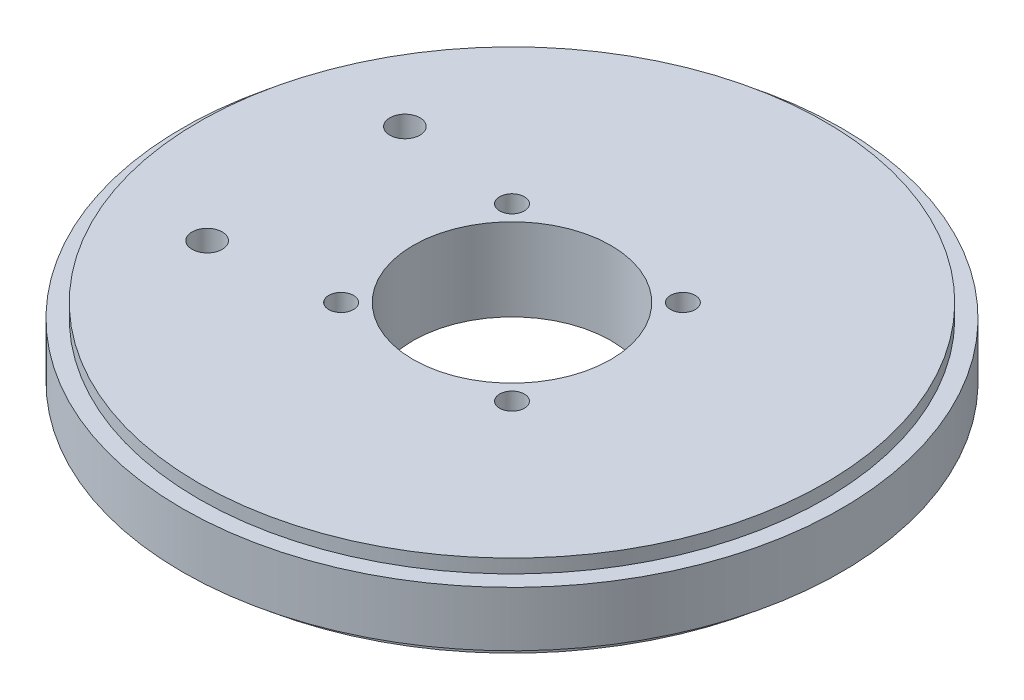
SolidWorks part; units mm, degrees
ref_plane "Front Plane" through (0, 0, 0) normal (0, 0, 1) x (1, 0, 0)
ref_plane "Top Plane" through (0, 0, 0) normal (0, 1, 0) x (1, 0, 0)
ref_plane "Right Plane" through (0, 0, 0) normal (1, 0, 0) x (0, 0, -1)
sketch "Sketch1" plane through (0, 0, 0) normal (0, 1, 0) x (1, 0, 0)
  circle A0 centre (0, 0) radius 57
  circle A1 centre (0, 0) radius 60
  dimension "D1" = 120
  dimension "D2" = 114
extrude "Extrude4" add sketch "Sketch1" along normal mid plane 15 contours A0
extrude "Extrude5" add sketch "Sketch" along normal mid plane 10
sketch "Sketch" plane through (0, 0, 0) normal (0, 1, 0) x (1, 0, 0) same geometry as "Sketch1"
sketch "Sketch5" plane through (0, 0, 0) normal (0, 1, 0) x (1, 0, 0)
  circle A0 centre (0, 0) radius 18
  dimension "D1" = 36
extrude "Extrude6" cut sketch "Sketch5" against normal through all both and the other way through all
hole_wizard "Ø4.5 (4.5) Diameter Hole1" positions "Sketch10" profile "Sketch11" hole size "Ø4.5" standard "ISO" end condition through all
sketch "Sketch10" plane through (0, -7.5, 0) normal (0, -1, 0) x (-1, 0, 0)
  point P6 (15.5563, 15.5563)
sketch "Sketch11" plane through (-15.5563, -7.5, -15.5563) normal (1, 0, 0) x (0, 0, -1)
  line L0 (0, 0) -> (0, 15)
  line L1 (0, 15) -> (2.25, 15)
  line L2 (2.25, 15) -> (2.25, 0)
  line L5 (2.25, 0) -> (0, 0)
  line L11 (0, -6.35) -> (0, 107.95) construction
  dimension "Thru Hole Dia." = 4.5
  dimension "Thru Hole Depth" = 15
ref_axis "Axis1" through (0, -8.25, 0) along (0, 1, 0)
pattern_circular "CirPattern1" count 4 over 360 about axis through (0, -8.25, 0) along (0, 1, 0) of "Ø4.5 (4.5) Diameter Hole1"
hole_wizard "M5 Clearance Hole1" positions "Sketch14" profile "Sketch15" hole size "M5" standard "ISO" end condition through all
sketch "Sketch14" plane through (0, 7.5, 0) normal (0, 1, 0) x (1, 0, 0)
  point P0 (-37.5, 18)
  point P3 (-37.5, -18)
sketch "Sketch15" plane through (-37.5, 7.5, -18) normal (1, 0, 0) x (0, 0, 1)
  line L0 (0, 0) -> (0, 15)
  line L1 (0, 15) -> (2.75, 15)
  line L2 (2.75, 15) -> (2.75, 0)
  line L5 (2.75, 0) -> (0, 0)
  line L11 (0, -6.35) -> (0, 107.95) construction
  dimension "Thru Hole Dia." = 5.5
  dimension "Thru Hole Depth" = 15
